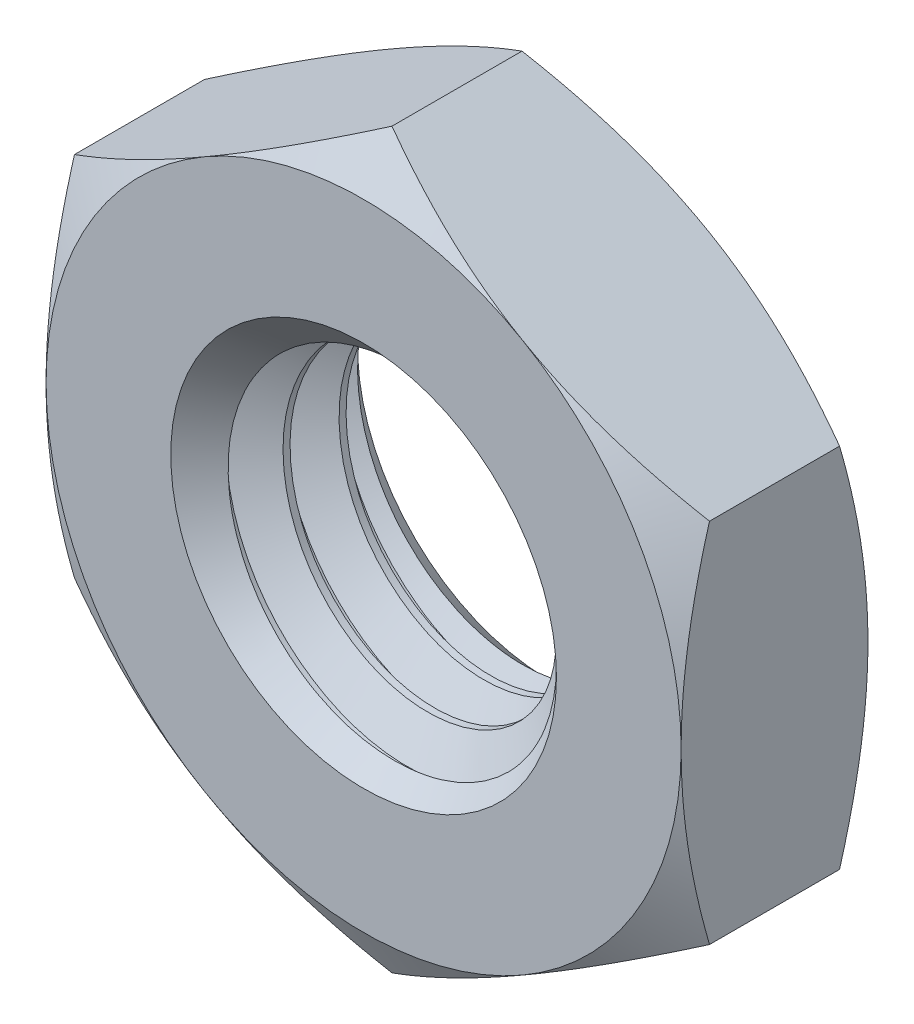
SolidWorks part; units mm, degrees
note: '?' marks a value the reader was unsure of.
ref_plane "Front Plane" through (0, 0, 0) normal (0, 0, 1) x (1, 0, 0)
ref_plane "Top Plane" through (0, 0, 0) normal (0, 1, 0) x (1, 0, 0)
ref_plane "Right Plane" through (0, 0, 0) normal (1, 0, 0) x (0, 0, -1)
sketch "Sketch1" plane through (0, 0, 0) normal (0, 0, 1) x (1, 0, 0)
  line L0 (0, 0) -> (-4.25, -7.3612) construction
  line L1 (0, 9.815) -> (-8.5, 4.9075) construction
  line L2 (-8.5, 4.9075) -> (-8.5, -4.9075) construction
  line L3 (-8.5, -4.9075) -> (0, -9.815) construction
  line L4 (0, -9.815) -> (8.5, -4.9075) construction
  line L5 (8.5, -4.9075) -> (8.5, 4.9075) construction
  line L6 (8.5, 4.9075) -> (0, 9.815) construction
  circle A0 centre (0, 0) radius 8.5 construction
  circle A1 centre (0, 0) radius 5 construction
  point P10 (-2.5, -4.3301)
  dimension "Thread Size" = 10
  dimension "Width" = 17
sketch "Sketch2" plane through (0, 0, 0) normal (1, 0, 0) x (0, 0, -1)
  line L0 (-2.5, 0) -> (2.5, 0) construction
  line L2 (2.5, 0) -> (2.5, 9.815) construction
  line L3 (2.5, 9.815) -> (-2.5, 9.815) construction
  line L4 (-2.5, 9.815) -> (-2.5, 0) construction
  line L5 (-2.5, 0) -> (-2.5, -9.815) construction
  line L6 (-2.5, -9.815) -> (2.5, -9.815) construction
  line L7 (2.5, -9.815) -> (2.5, 0) construction
  line L8 (-2.5, 5) -> (2.5, 5) construction
  line L9 (-2.5, -5) -> (2.5, -5) construction
  line L11 (-3.9062, 5.1624) -> (-3.1562, 3.8633) construction
  line L12 (-3.1562, 3.8633) -> (-2.4062, 5.1624) construction
  line L13 (-2.4062, 5.1624) -> (-3.9062, 5.1624) construction
  line L14 (-3.1562, 3.8633) -> (-3.1562, 4.0257) construction
  line L15 (-3.25, 4.0257) -> (-3.0625, 4.0257) construction
  line L16 (-3.1562, 5.1624) -> (-3.1562, 5) construction
  line L17 (-3.8125, 5) -> (-2.5, 5) construction
  line L18 (-3.1562, 5.0812) -> (-2.4531, 5.0812) construction
  line L19 (-3.1562, 5.0812) -> (-3.8594, 5.0812) construction
  point P4 (0, 0)
  point P17 (0, 5)
  point P19 (0, -5)
  dimension "Height" = 5
  dimension "Pitch" = 1.5
  dimension "D1" = 0.1875
sketch "Sketch3" plane through (0, 0, 0) normal (0, 0, 1) x (1, 0, 0)
  line L0 (-8.5, -4.9075) -> (0, -9.815) construction
  line L1 (0, -9.815) -> (8.5, -4.9075) construction
  line L2 (8.5, -4.9075) -> (8.5, 4.9075) construction
  line L3 (8.5, 4.9075) -> (0, 9.815) construction
  line L4 (0, 9.815) -> (-8.5, 4.9075) construction
  line L5 (-8.5, 4.9075) -> (-8.5, -4.9075) construction
  line L6 (-8.5, -4.9075) -> (0, -9.815)
  line L7 (0, -9.815) -> (8.5, -4.9075)
  line L8 (8.5, -4.9075) -> (8.5, 4.9075)
  line L9 (8.5, 4.9075) -> (0, 9.815)
  line L10 (0, 9.815) -> (-8.5, 4.9075)
  line L11 (-8.5, 4.9075) -> (-8.5, -4.9075)
  circle A0 centre (0, 0) radius 5 construction
  circle A1 centre (0, 0) radius 5
extrude "Boss-Extrude1" add sketch "Sketch3" against normal up to vertex (2.5 mm away) from vertex at 2.5 starting at point (0, 0, 2.5)
sketch "Sketch4" plane through (0, 0, 0) normal (0, 0, 1) x (1, 0, 0)
  circle A0 centre (0, 0) radius 8.5 construction
  circle A1 centre (0, 0) radius 8.5
extrude "Cut-Extrude1" cut sketch "Sketch4" against normal through all draft 60 from vertex at 2.5 flip side to cut starting at point (0, 0, 2.5)
sketch "Sketch5" plane through (0, 0, 0) normal (0, 0, 1) x (1, 0, 0)
  circle A0 centre (0, 0) radius 8.5 construction
  circle A1 centre (0, 0) radius 8.5
extrude "Cut-Extrude2" cut sketch "Sketch5" along normal through all draft 60 from vertex at -2.5 flip side to cut starting at point (0, 0, -2.5)
sketch "Sketch6" plane through (0, 0, 2.5) normal (0, 0, 1) x (1, 0, 0)
  circle A0 centre (0, 0) radius 5
  point P0 (0, 5)
sketch "Sketch8" plane through (0, 0, 0) normal (0, 0, 1) x (1, 0, 0)
  circle A0 centre (0, 0) radius 5.1624
sketch "Sketch9" plane through (0, 0, 0) normal (0, 0, 1) x (1, 0, 0)
  circle A1 centre (0, 0) radius 5.1624
  circle A2 centre (0, 0) radius 5.1624
  dimension "D1" = 0
ref_axis "Center Axis 1" through (0, 0, 2.5) along (0, 0, -1)?
curve "Helix/Spiral1" pitch 1.5 height 6.5 turns 4.3333
sketch "Sketch7" plane through (0, 0, 0) normal (1, 0, 0) x (0, 0, -1)
  line L0 (-3.8594, 5.0812) -> (-3.25, 4.0257)
  line L1 (-3.25, 4.0257) -> (-3.0625, 4.0257)
  line L2 (-3.0625, 4.0257) -> (-2.4531, 5.0812)
  line L3 (-2.4531, 5.0812) -> (-3.8594, 5.0812)
sweep "Sweep1" add profiles "Sketch7" path "Helix/Spiral1"
extrude "Cut-Extrude3" cut sketch "Sketch8" against normal through all draft 45 and the other way through all draft 45 from vertex at 2.5
extrude "Cut-Extrude4" cut sketch "Sketch9" along normal through all draft 45 and the other way through all draft 45 from vertex at -2.5
equation "\"D1@Sketch2\"=\"Pitch@Sketch2\"/8"
equation "\"D4@Helix/Spiral1\"=\"Pitch@Sketch2\""
equation "\"D3@Helix/Spiral1\"=\"Height@Sketch2\"+\"Pitch@Sketch2\""
